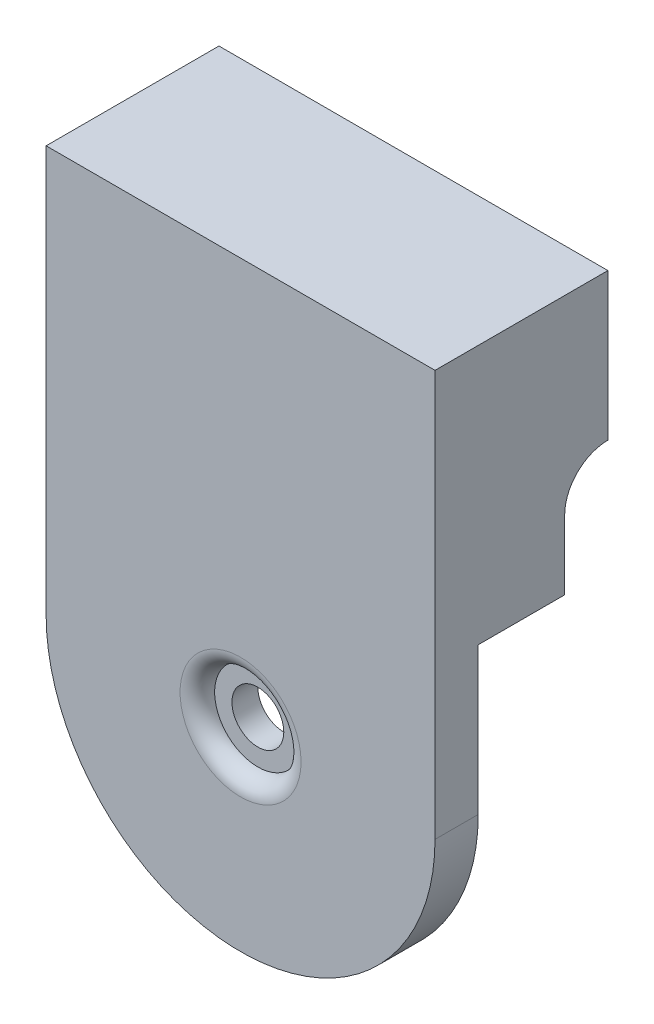
SolidWorks part; units mm, degrees
ref_plane "Front Plane" through (0, 0, 0) normal (0, 0, 1) x (1, 0, 0)
ref_plane "Top Plane" through (0, 0, 0) normal (0, 1, 0) x (1, 0, 0)
ref_plane "Right Plane" through (0, 0, 0) normal (1, 0, 0) x (0, 0, -1)
sketch "Esboço2" plane through (0, 0, 0) normal (0, 0, 1) x (1, 0, 0)
  line L0 (-22.5, 0) -> (-22.5, 30)
  line L1 (-22.5, 30) -> (22.5, 30)
  line L2 (22.5, 30) -> (22.5, 0)
  circle A0 centre (0, 0) radius 3
  arc A1 (-22.5, 0) -> (22.5, 0) centre (0, 0) ccw
  dimension "D1" = 6
  dimension "D2" = 22.5
  dimension "D3" = 30
  dimension "D4" = 45
extrude "Ressalto-extrusão1" add sketch "Esboço2" along normal blind 5
sketch "Esboço7" plane through (0, 0, 5) normal (0, 0, 1) x (1, 0, 0)
  circle A0 centre (0, 0) radius 5
  dimension "D1" = 10
extrude "Corte-extrusão2" cut sketch "Esboço7" against normal blind 2
sketch "Esboço3" plane through (0, 0, 0) normal (0, 0, -1) x (-1, 0, 0)
  line L0 (-22.5, 17) -> (22.5, 17)
  line L1 (-22.5, 0) -> (-22.5, 30) construction
  line L2 (22.5, 30) -> (22.5, 0) construction
  line L3 (22.5, 17) -> (22.5, 30)
  line L4 (22.5, 30) -> (-22.5, 30)
  line L5 (-22.5, 30) -> (-22.5, 17)
  line L6 (-22.5, 30) -> (22.5, 30) construction
  dimension "D1" = 17
extrude "Ressalto-extrusão2" add sketch "Esboço3" along normal blind 10
sketch "Esboço4" plane through (0, 30, 0) normal (0, 1, 0) x (1, 0, 0)
  line L14 (-22.5, -5) -> (-22.5, 15)
  line L15 (-22.5, 15) -> (22.5, 15)
  line L16 (22.5, 15) -> (22.5, -5)
  line L17 (22.5, -5) -> (-22.5, -5)
  dimension "D1" = 20
extrude "Ressalto-extrusão3" add sketch "Esboço4" along normal blind 17
sketch "Esboço6" plane through (0, 0, -15) normal (0, 0, -1) x (-1, 0, 0)
  line L0 (22.5, 47) -> (22.5, 30) construction
  line L1 (-22.5, 30) -> (22.5, 30) construction
  line L2 (-22.5, 47) -> (-22.5, 30) construction
  line L3 (-22.5, 47) -> (22.5, 47) construction
  line L4 (22.5, 47) -> (22.5, 30)
  line L5 (-22.5, 30) -> (22.5, 30)
  line L6 (-22.5, 47) -> (-22.5, 30)
  line L7 (-22.5, 47) -> (22.5, 47)
  line L8 (15.25, 41.75) -> (15.25, 35.25)
  line L9 (-15.25, 35.25) -> (15.25, 35.25)
  line L10 (-15.25, 41.75) -> (-15.25, 35.25)
  line L11 (-15.25, 41.75) -> (15.25, 41.75)
  point P8 (15.25, 38.5)
  point P9 (22.5, 38.5)
  point P10 (0, 41.75)
  point P11 (0, 47)
  dimension "D1" = 6.5
  dimension "D2" = 30.5
extrude "Corte-extrusão1" cut sketch "Esboço6" against normal blind 15 contours L8 L9 L10 L11
fillet "Filete4" radius 5 1 edges at (0, 30, -10)
fillet "Filete5" radius 2 1 edges at (5, 0, 5)
